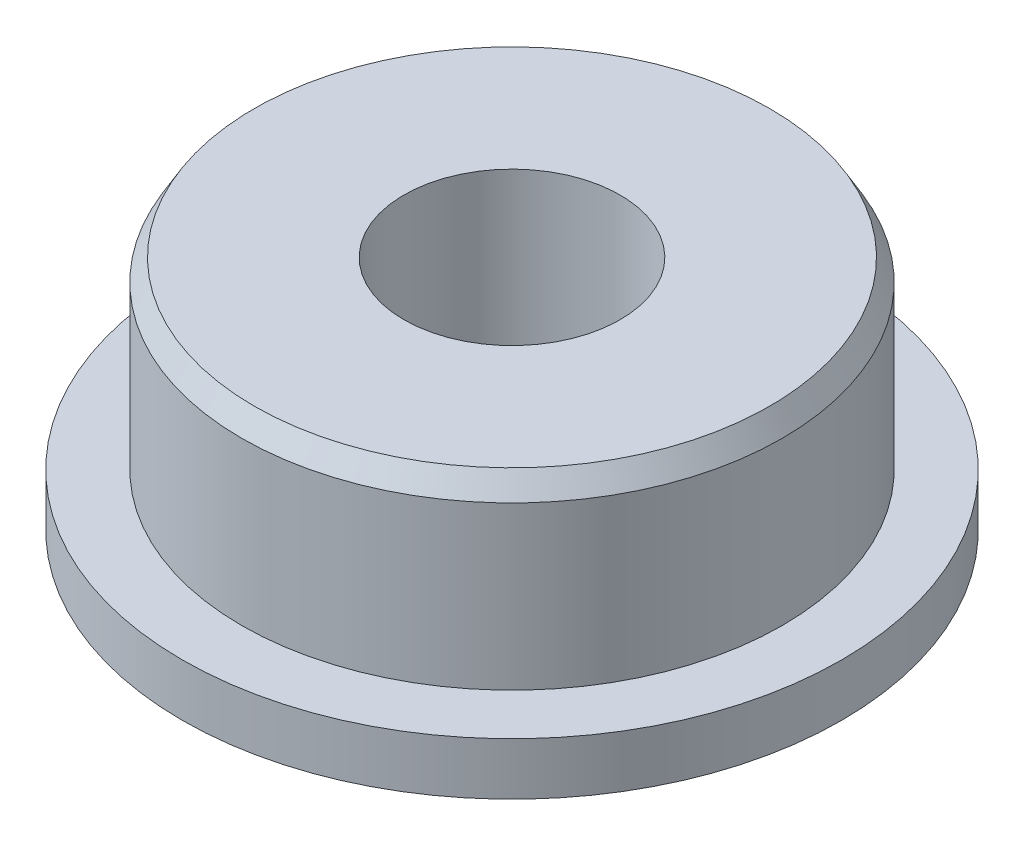
SolidWorks part; units mm, degrees
material "AISI 1045 钢，冷拔"
ref_plane "前视基准面" through (0, 0, 0) normal (0, 0, 1) x (1, 0, 0)
ref_plane "上视基准面" through (0, 0, 0) normal (0, 1, 0) x (1, 0, 0)
ref_plane "右视基准面" through (0, 0, 0) normal (1, 0, 0) x (0, 0, -1)
sketch "草图1" plane through (0, 0, 0) normal (0, 1, 0) x (1, 0, 0)
  circle A0 centre (0, 0) radius 1
  circle A1 centre (0, 0) radius 2.5
  circle A2 centre (0, 0) radius 3.05
  dimension "d" = 2
  dimension "D " = 5
  dimension "法兰外径" = 6.1
extrude "凸台-拉伸1" add sketch "草图1" along normal blind 2.3 contours A1 A0 region at (-2.4293, 0, 0)
extrude "凸台-拉伸2" add sketch "草图1<3>" along normal blind 0.6 contours A2 A1 region at (-2.9637, 0, 0)
sketch "草图1<3>" plane through (0, 0, 0) normal (0, 1, 0) x (1, 0, 0) same geometry as "草图1"
chamfer "倒角1" distance 0.2 angle 30 2 edges at (0, 2.3, 2.5) (0, 0, 3.05) first distance on face at (0, 0.6, 2.5) first distance on face at (0, 0, 1)
